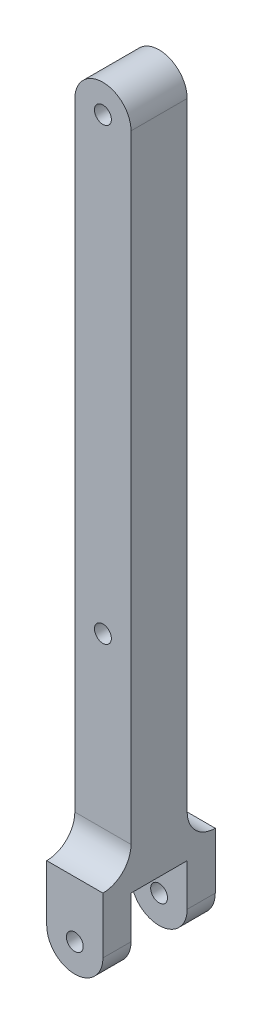
SolidWorks part; units mm, degrees
ref_plane "Alzado" through (0, 0, 0) normal (0, 0, 1) x (1, 0, 0)
ref_plane "Planta" through (0, 0, 0) normal (0, 1, 0) x (1, 0, 0)
ref_plane "Vista lateral" through (0, 0, 0) normal (1, 0, 0) x (0, 0, -1)
sketch "Croquis1" plane through (0, 0, 0) normal (0, 0, 1) x (1, 0, 0)
  line L0 (0, 0) -> (0, -125) construction
  line L1 (5, 0) -> (5, -125)
  line L2 (-5, 0) -> (-5, -125)
  arc A0 (5, 0) -> (-5, 0) centre (0, 0) ccw
  arc A1 (-5, -125) -> (5, -125) centre (0, -125) ccw
  circle A2 centre (0, 0) radius 1.5
  circle A3 centre (0, -125) radius 1.5
  circle A4 centre (0, -80) radius 1.5
  point P3 (0, -62.5)
  dimension "D2" = 5
  dimension "D3" = 3
  dimension "D1" = 125
  dimension "D4" = 80
extrude "Saliente-Extruir1" add sketch "Croquis1" along normal blind 10
sketch "Croquis2" plane through (0, 0, 10) normal (0, 0, 1) x (1, 0, 0)
  line L0 (0, 5) -> (-44.5846, 5) construction
  line L1 (0, -130) -> (-39.3393, -130) construction
  line L2 (0, -115) -> (-44.5846, -115) construction
  line L3 (-5, -125) -> (-5, -115)
  line L4 (-5, 0) -> (-5, -125) construction
  line L5 (-5, -115) -> (5, -115)
  line L6 (5, -125) -> (5, 0) construction
  line L7 (5, -115) -> (5, -125)
  arc A0 (5, 0) -> (-5, 0) centre (0, 0) ccw construction
  arc A1 (-5, -125) -> (5, -125) centre (0, -125) ccw construction
  arc A2 (-5, -125) -> (5, -125) centre (0, -125) ccw
  circle A4 centre (0, -125) radius 1.5 construction
  circle A5 centre (0, -125) radius 1.5
  dimension "D1" = 15
sketch "Croquis3" plane through (0, 0, 0) normal (0, 0, 1) x (1, 0, 0)
  line L0 (-5, -125) -> (-5, -115) construction
  line L1 (-5, -115) -> (5, -115) construction
  line L2 (5, -115) -> (5, -125) construction
  line L3 (-5, -125) -> (-5, -115)
  line L4 (-5, -115) -> (5, -115)
  line L5 (5, -115) -> (5, -125)
  arc A0 (-5, -125) -> (5, -125) centre (0, -125) ccw construction
  arc A1 (-5, -125) -> (5, -125) centre (0, -125) ccw
  circle A3 centre (0, -125) radius 1.5
  dimension "D1" = 3
extrude "Saliente-Extruir2" add sketch "Croquis3" against normal blind 5
sketch "Croquis5" plane through (-5, 0, 0) normal (-1, 0, 0) x (0, 0, 1)
  line L0 (-5, -130) -> (10, -130) construction
  line L1 (0, -130) -> (10, -130)
  line L2 (0, -130) -> (0, -117.5)
  line L3 (0, -117.5) -> (10, -117.5)
  line L4 (10, -130) -> (10, -117.5)
  line L5 (-5, -115) -> (-5, -125) construction
  dimension "D1" = 12.5
  dimension "D2" = 10
  dimension "D3" = 5
extrude "Cortar-Extruir1" cut sketch "Croquis5" against normal blind 16
extrude "Saliente-Extruir3" add sketch "Croquis2" along normal blind 5
fillet "Redondeo1" radius 5 2 edges
